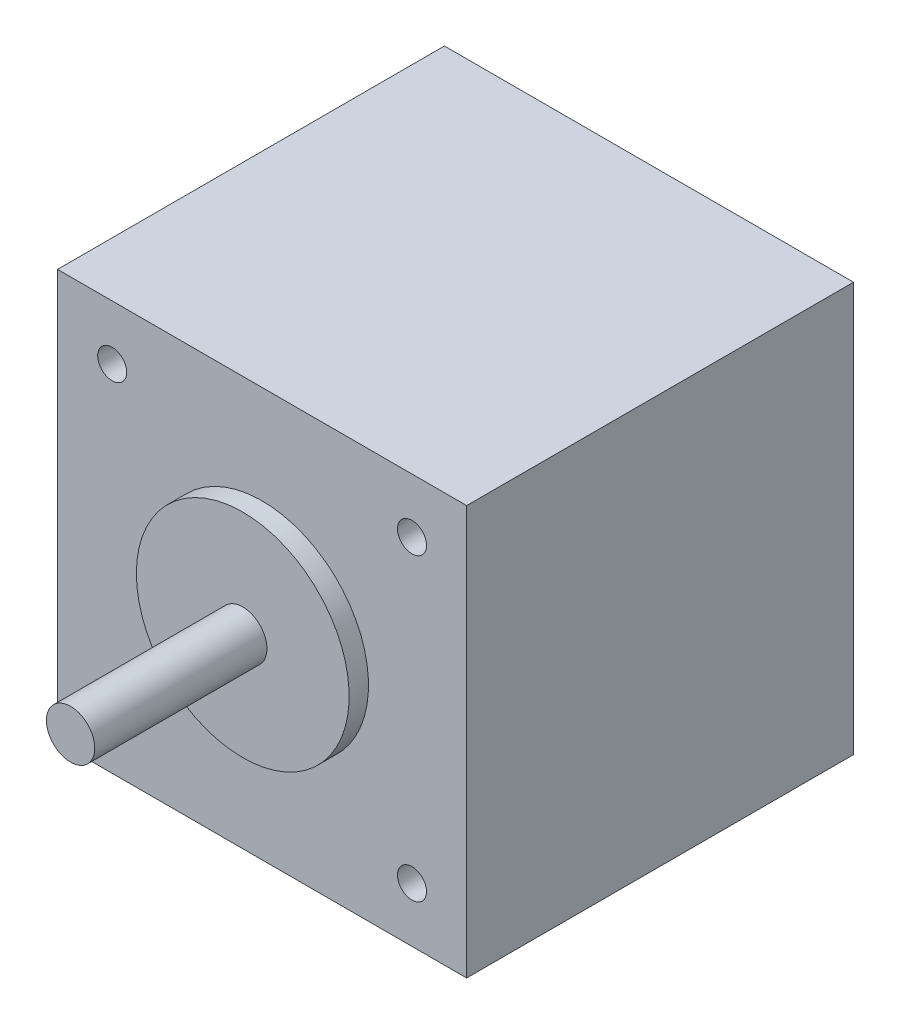
SolidWorks part; units mm, degrees
ref_plane "Спереди" through (0, 0, 0) normal (0, 0, 1) x (1, 0, 0)
ref_plane "Сверху" through (0, 0, 0) normal (0, 1, 0) x (1, 0, 0)
ref_plane "Справа" through (0, 0, 0) normal (1, 0, 0) x (0, 0, -1)
other "Configuration Table"
sketch "Эскиз1" plane through (0, 0, 0) normal (0, 0, 1) x (1, 0, 0)
  line L1 (-21.15, -21.15) -> (21.15, -21.15)
  line L2 (-21.15, -21.15) -> (-21.15, 21.15)
  line L3 (-21.15, 21.15) -> (21.15, 21.15)
  line L4 (21.15, -21.15) -> (21.15, 21.15)
  line L5 (-21.15, -21.15) -> (21.15, 21.15) construction
  line L6 (-21.15, 21.15) -> (21.15, -21.15) construction
  point P0 (0, 0)
  dimension "D1" = 42.3
  dimension "D2" = 42.3
extrude "Корпус" add sketch "Эскиз1" along normal blind 40
sketch "Эскиз2" plane through (0, 0, 0) normal (0, 0, 1) x (1, 0, 0)
  circle A0 centre (0, 0) radius 2.5
extrude "Вал_ПРЕДВ" add sketch "Эскиз2" along normal blind 59.8
sketch "Эскиз3" plane through (0, 0, 0) normal (0, 0, 1) x (1, 0, 0)
  circle A0 centre (0, 0) radius 11
  dimension "D1" = 22
extrude "Буртик_ПРЕДВ" add sketch "Эскиз3" along normal blind 42
sketch "Эскиз4" plane through (0, 0, 0) normal (0, 0, 1) x (1, 0, 0)
  circle A0 centre (0, 0) radius 8
  dimension "D1" = 16
sketch "Эскиз5" plane through (0, 0, 0) normal (0, 0, 1) x (1, 0, 0)
  circle A0 centre (-15.5, -15.5) radius 1.5
  circle A1 centre (-15.5, 15.5) radius 1.5
  circle A2 centre (15.5, -15.5) radius 1.5
  circle A3 centre (15.5, 15.5) radius 1.5
  dimension "D1" = 3
  dimension "D2" = 3
  dimension "D3" = 3
  dimension "D4" = 3
extrude "Крепеж_М3_ПРЕДВ" cut sketch "Эскиз5" against normal blind 4.5 from offset 40
equation "\"Мотор X ширина корпуса\"= 42.3"
equation "\"Мотор X высота корпуса\"= 42.3"
equation "\"Мотор X длина корпуса\"= 40"
equation "\"Мотор X вылет вала\"= 19.8"
equation "\"Мотор Y ширина корпуса\"= 42.3"
equation "\"Мотор Y высота корпуса\"= 42.3"
equation "\"Мотор Y длина корпуса\"= 48"
equation "\"Мотор Y вылет вала\"= 30"
equation "\"Мотор Z ширина корпуса\"= 42"
equation "\"Мотор Z высота корпуса\"= 42"
equation "\"Мотор Z длина корпуса\"= 40"
equation "\"Мотор Z вылет вала\"= 23"
equation "\"Мотор диаметр вала ПРЕДВ\"= 5"
equation "\"Мотор шаг крепления ПРЕДВ\"= 31"
equation "\"Мотор диаметр отверстий ПРЕДВ\"= 3"
equation "\"Мотор глубина отверстий ПРЕДВ\"= 4.5"
equation "\"Мотор диаметр буртика ПРЕДВ\"= 22"
equation "\"Мотор высота буртика ПРЕДВ\"= 2"
equation "\"Мотор диаметр шкива ПРЕДВ\"= 16"
equation "\"Мотор длина шкива ПРЕДВ\"= 12"
equation "\"Мотор отступ шкива ПРЕДВ\"= 5"
equation "\"Мотор X шаг градусов\"= 1.8"
equation "\"Мотор Y шаг градусов\"= 1.8"
equation "\"Мотор Z шаг градусов\"= 1.8"
equation "\"Мотор Y диаметр ротора\"= 25.78"
equation "\"D1@Эскиз1\" = \"Мотор X ширина корпуса\""
equation "\"D1@Корпус\" = \"Мотор X длина корпуса\""
equation "\"D1@Эскиз2\" = \"Мотор диаметр вала ПРЕДВ\""
equation "\"D1@Вал_ПРЕДВ\" = \"Мотор X длина корпуса\" + \"Мотор X вылет вала\""
equation "\"D1@Эскиз3\" = \"Мотор диаметр буртика ПРЕДВ\""
equation "\"D1@Буртик_ПРЕДВ\" = \"Мотор X длина корпуса\" + \"Мотор высота буртика ПРЕДВ\""
equation "\"D1@Эскиз4\" = \"Мотор диаметр шкива ПРЕДВ\""
equation "\"D1@Эскиз5\" = \"Мотор диаметр отверстий ПРЕДВ\""
equation "\"D2@Эскиз5\" = \"Мотор диаметр отверстий ПРЕДВ\""
equation "\"D3@Эскиз5\" = \"Мотор диаметр отверстий ПРЕДВ\""
equation "\"D4@Эскиз5\" = \"Мотор диаметр отверстий ПРЕДВ\""
equation "\"D1@Крепеж_М3_ПРЕДВ\" = \"Мотор глубина отверстий ПРЕДВ\""
equation "\"D19@Крепеж_М3_ПРЕДВ\" = \"Мотор X длина корпуса\""
equation "\"Ширина груза\"= 420"
equation "\"Глубина груза\"= 490"
equation "\"Высота груза\"= 297"
equation "\"Ширина ячейки\"= \"Ширина груза\" + 10"
equation "\"Глубина ячейки\"= \"Глубина груза\" + 10"
equation "\"Высота ячейки\"= \"Высота груза\" + 10 + 13"
equation "\"Колво ячеек ширина\"= 2"
equation "\"Колво ячеек высота\"= 2"
equation "\"Толщина стенки\"= 10"
equation "\"Крепление дверцы\"= 5"
equation "\"Ширина рейки\"= \"Толщина шестерни\""
equation "\"Высота рейки\"= 20"
equation "\"Высота пола\"= 20"
equation "\"Колво полозьев\"= 5"
equation "\"Отступ рейки\"= 20"
equation "\"Глубина каретки\"= \"Глубина ячейки\" + 30 + \"Мотор Y высота корпуса\" + 20"
equation "\"Отступ шпильки\"= 26"
equation "\"Диаметр шпильки\"= 5"
equation "\"Длинна шпильки\"= ( \"Высота ячейки\" + \"Толщина стенки\" + \"Высота пола\" ) * \"Колво ячеек высота\" + ( \"Толщина стенки\" + \"Отступ рейки\" ) * 2 "
equation "\"Ширина пластины\"= 50  "
equation "\"Высота зона выгрузки\"= \"Высота ячейки\" * 2 + \"Толщина стенки\" * 2"
equation "\"Колво выгрузки\"= 1"
equation "\"Отступ крепления мотора фиксации\" = 30"
equation "\"Диаметр оси\"= 10"
equation "\"Диаметр ролика\"= 20"
equation "\"Колво роликов\"= 10"
equation "\"Шаг роликов\"= \"Диаметр ролика\" + 20"
equation "\"Ширина ячейки выгрузки\"= \"Ширина ячейки\" + \"Толщина стенки\" + \"Отступ крепления мотора фиксации\"*2"
equation "\"Длинна рейки\"= ( \"Ширина ячейки\" + \"Толщина стенки\" + \"Крепление дверцы\" ) * \"Колво ячеек ширина\" + \"Ширина ячейки выгрузки\" * \"Колво выгрузки\" + \"Толщина стенки\""
equation "\"Толщина шестерни\"= 10"
